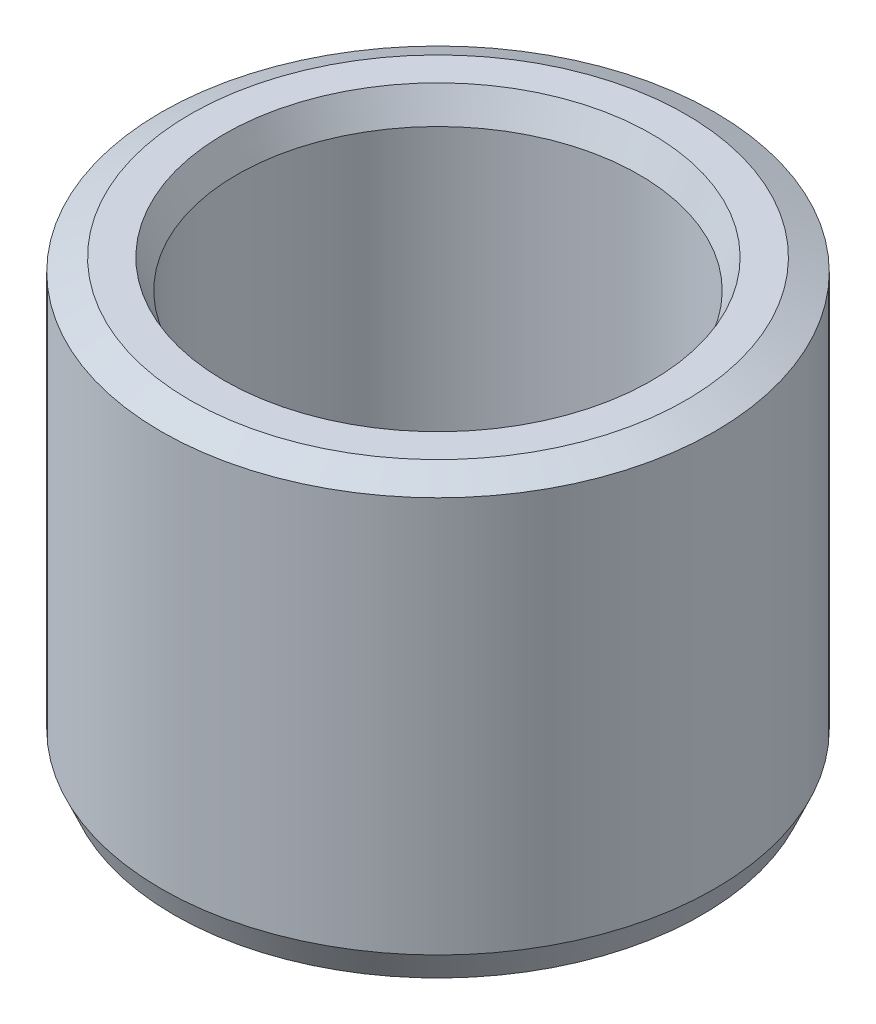
SolidWorks part; units mm, degrees
ref_plane "Front Plane" through (0, 0, 0) normal (0, 0, 1) x (1, 0, 0)
ref_plane "Top Plane" through (0, 0, 0) normal (0, 1, 0) x (1, 0, 0)
ref_plane "Right Plane" through (0, 0, 0) normal (1, 0, 0) x (0, 0, -1)
sketch "Sketch1" plane through (0, 0, 0) normal (0, 1, 0) x (1, 0, 0)
  circle A0 centre (0, 0) radius 57.5
  dimension "SLEEVE_OD" = 115
extrude "Boss-Extrude1" add sketch "Sketch1" along normal blind 90.9257
sketch "Sketch2" plane through (0, 0, 0) normal (0, 1, 0) x (1, 0, 0)
  circle A0 centre (0, 0) radius 41.7719
  dimension "BORE_D" = 83.5439
extrude "Cut-Extrude1" cut sketch "Sketch2" along normal through all
chamfer "Chamfer1" distance 2.632 angle 66.311 4 edges at (0, 90.9257, 41.7719) (0, 0, 41.7719) (0, 0, 57.5) (0, 90.9257, 57.5) first distance on face at (0, 90.9257, 41.7719) first distance on face at (0, 0, 41.7719) first distance on face at (0, 90.9257, 57.5)
